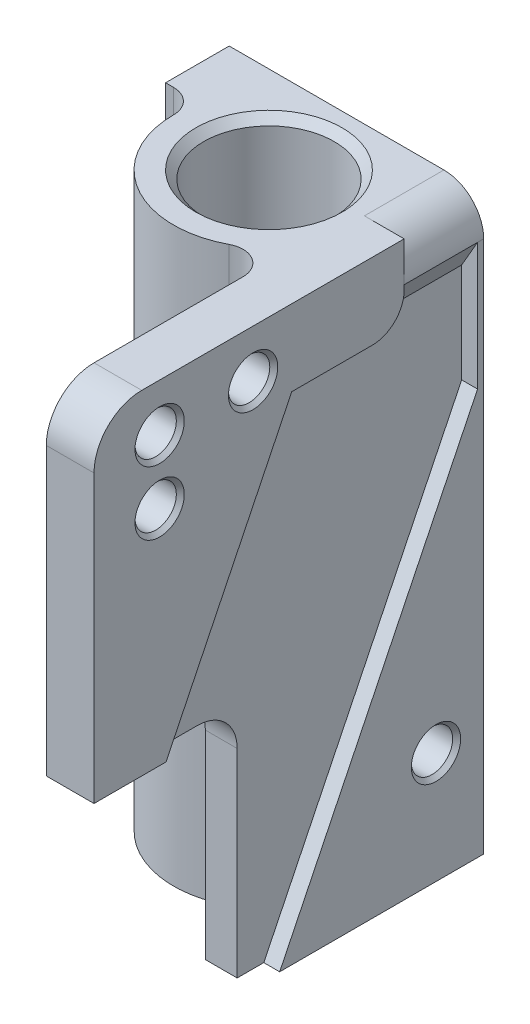
SolidWorks part; units mm, degrees
ref_plane "Front Plane" through (0, 0, 0) normal (0, 0, 1) x (1, 0, 0)
ref_plane "Top Plane" through (0, 0, 0) normal (0, 1, 0) x (1, 0, 0)
ref_plane "Right Plane" through (0, 0, 0) normal (1, 0, 0) x (0, 0, -1)
sketch "Sketch1" plane through (0, 0, 0) normal (0, 1, 0) x (1, 0, 0)
  line L1 (-16, 11) -> (16, 11)
  line L2 (-16, 11) -> (-16, 3)
  line L3 (-16, 3) -> (-15, 3)
  line L4 (16, 11) -> (16, -38)
  line L6 (16, -38) -> (10, -38)
  line L7 (10, -38) -> (10, -13.2665)
  circle A0 centre (0, 0) radius 8.2
  arc A1 (-12, 0) -> (5.6, -10.6132) centre (0, 0) ccw
  arc A2 (5.6, -10.6132) -> (10, -13.2665) centre (7, -13.2665) cw
  arc A3 (-12, 0) -> (-15, 3) centre (-15, 0) ccw
  dimension "D1" = 16.4
  dimension "D2" = 12
  dimension "D6" = 3
  dimension "D8" = 49
  dimension "D10" = 6
  dimension "D7" = 3
  dimension "D3" = 32
  dimension "D4" = 8
  dimension "D5" = 11
  dimension "D9" = 16
extrude "Boss-Extrude1" add sketch "Sketch1" along normal blind 72
sketch "Sketch2" plane through (0, 0, -11) normal (0, 0, 1) x (1, 0, 0)
  line L0 (-11, 67) -> (11, 5) construction
  line L1 (0, 36) -> (0, 0) construction
  line L2 (-16, 36) -> (0, 36) construction
  line L3 (-16, 72) -> (-16, 0) construction
  line L4 (10, 72) -> (16, 72) construction
  circle A0 centre (-11, 67) radius 2.6
  circle A1 centre (-11, 5) radius 2.6
  circle A2 centre (11, 67) radius 2.6
  circle A3 centre (11, 5) radius 2.6
  point P12 (13, 72)
  dimension "D1" = 5.2
  dimension "D2" = 5
  dimension "D3" = 5
extrude "Cut-Extrude1" cut sketch "Sketch2" along normal blind 6
chamfer "Chamfer1" distance 0.5 angle 45 4 edges at (-8.4, 5, -11) (13.6, 5, -11) (13.6, 67, -11) (-8.4, 67, -11)
chamfer "Chamfer2" distance 1 angle 45 2 edges at (0, 0, 8.2) (0, 72, 8.2)
sketch "Sketch3" plane through (16, 0, 0) normal (1, 0, 0) x (0, 0, -1)
  line L0 (-38, 72) -> (-38, 0) construction
  line L1 (-38, 72) -> (11, 72) construction
  circle A0 centre (-29.75, 66) radius 2.6
  circle A1 centre (-29.75, 58) radius 2.6
  dimension "D3" = 5.2
  dimension "D1" = 8
  dimension "D2" = 8.25
  dimension "D4" = 6
extrude "Cut-Extrude2" cut sketch "Sketch3" against normal through all
sketch "Sketch4" plane through (0, 0, -11) normal (0, 0, -1) x (-1, 0, 0)
  line L0 (-11, 72) -> (-16, 72)
  line L1 (-16, 72) -> (-16, 67)
  arc A0 (-11, 72) -> (-16, 67) centre (-11, 67) ccw
extrude "Cut-Extrude3" cut sketch "Sketch4" against normal blind 10
sketch "Sketch5" plane through (16, 0, 0) normal (1, 0, 0) x (0, 0, -1)
  line L0 (-13.1366, 62.4193) -> (10.232, 51.0217) construction
  line L1 (10.232, 51.0217) -> (-14.6529, 0)
  line L2 (10.232, 51.0217) -> (10.232, 62.4193)
  line L3 (-38, 11.4419) -> (-13.1366, 62.4193)
  line L4 (6, 72) -> (-1.4523, 56.7205) construction
  line L5 (1, 72) -> (11, 72) construction
  line L6 (11, 67) -> (11, 0) construction
  line L7 (10.232, 62.4193) -> (-13.1366, 62.4193)
  line L8 (-38, 72) -> (-38, 0) construction
  line L9 (-38, 0) -> (11, 0) construction
  line L10 (-14.6529, 0) -> (-38, 0)
  line L11 (-38, 0) -> (-38, 11.4419)
  dimension "D1" = 26
  dimension "D3" = 26
  dimension "D4" = 17
extrude "Cut-Extrude4" cut sketch "Sketch5" against normal blind 2
sketch "Sketch6" plane through (14, 0, 0) normal (1, 0, 0) x (0, 0, -1)
  line L0 (-38, 0) -> (-14.6529, 0) construction
  line L1 (-38, 0) -> (-18, 0)
  line L2 (-38, 0) -> (-38, 30)
  line L3 (-38, 30) -> (-23, 30)
  line L4 (-18, 0) -> (-18, 25)
  arc A0 (-23, 30) -> (-18, 25) centre (-23, 25) cw
  dimension "D3" = 5
  dimension "D1" = 20
  dimension "D2" = 30
extrude "Cut-Extrude5" cut sketch "Sketch6" against normal blind 10 and the other way blind 10
sketch "Sketch8" plane through (0, 0, -1) normal (0, 0, -1) x (-1, 0, 0)
  line L0 (-16, 67) -> (-16, 62.4193)
  line L1 (-16, 62.4193) -> (-14, 62.4193)
  line L2 (-14, 62.4193) -> (-14, 63.5359)
  line L3 (-14, 63.5359) -> (-16, 67)
  dimension "D1" = 30
extrude "Cut-Extrude6" cut sketch "Sketch8" along normal up to surface (9.232 mm away) up to face at (15, 56.7205, -10.232)
fillet "Fillet1" radius 4 1 edges at (15, 62.4193, -1)
fillet "Fillet2" radius 6 1 edges at (13, 72, 38)
sketch "Sketch9" plane through (16, 0, 0) normal (1, 0, 0) x (0, 0, -1)
  line L0 (-32, 72) -> (1, 72) construction
  line L1 (11, 67) -> (11, 72) construction
  line L2 (11, 67) -> (11, 0) construction
  line L4 (-14.6529, 0) -> (11, 0) construction
  circle A0 centre (-18, 66) radius 2.6
  circle A1 centre (5, 14) radius 2.6
  dimension "D5" = 5.2
  dimension "D1" = 6
  dimension "D2" = 29
  dimension "D3" = 6
  dimension "D4" = 14
extrude "Cut-Extrude7" cut sketch "Sketch9" against normal blind 6
chamfer "Chamfer3" distance 0.5 angle 45 4 edges at (16, 14, -7.6) (16, 66, 15.4) (16, 66, 27.15) (16, 58, 27.15)
